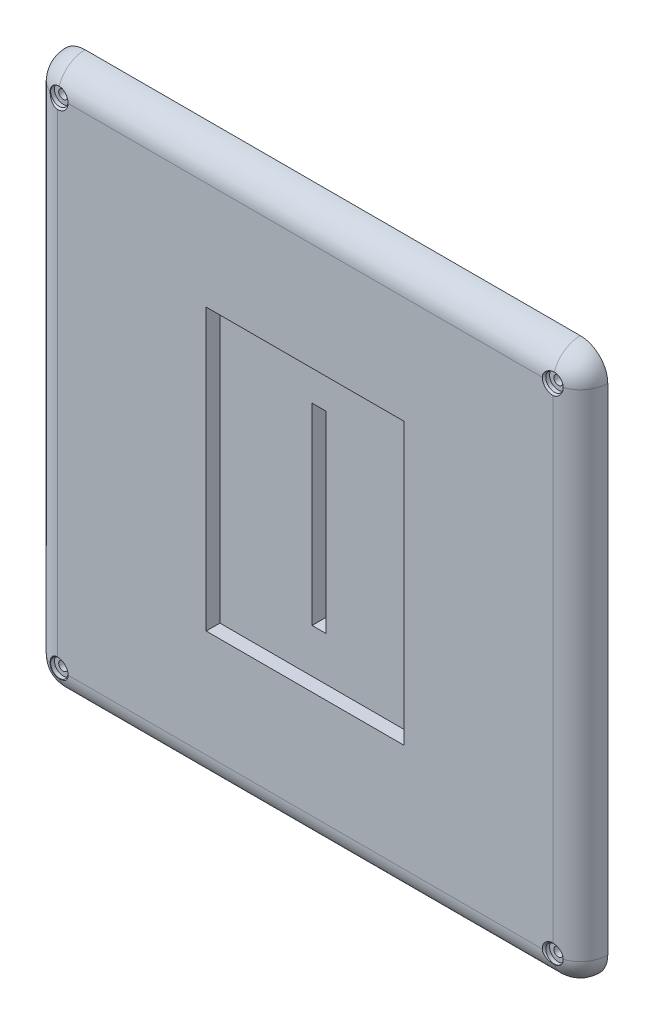
SolidWorks part; units mm, degrees
ref_plane "Alzado" through (0, 0, 0) normal (0, 0, 1) x (1, 0, 0)
ref_plane "Planta" through (0, 0, 0) normal (0, 1, 0) x (1, 0, 0)
ref_plane "Vista lateral" through (0, 0, 0) normal (1, 0, 0) x (0, 0, -1)
sketch "Croquis3" plane through (0, 0, 0) normal (0, 0, 1) x (1, 0, 0)
  line L1 (-100, -100) -> (100, -100)
  line L2 (-100, -100) -> (-100, 100)
  line L3 (-100, 100) -> (100, 100)
  line L4 (100, -100) -> (100, 100)
  line L5 (-100, -100) -> (100, 100) construction
  line L6 (-100, 100) -> (100, -100) construction
  point P0 (0, 0)
  dimension "D1" = 200
  dimension "D2" = 200
extrude "Saliente-Extruir1" add sketch "Croquis3" along normal blind 10
sketch "Croquis4" plane through (0, 0, 10) normal (0, 0, 1) x (1, 0, 0)
  line L0 (-100, -100) -> (100, -100) construction
  line L1 (0, -100) -> (0, 100) construction
  line L2 (100, 100) -> (-100, 100) construction
  line L4 (-36, 51) -> (36, 51)
  line L5 (-36, 51) -> (-36, -51)
  line L6 (-36, -51) -> (36, -51)
  line L7 (36, 51) -> (36, -51)
  line L8 (-36, 51) -> (36, -51) construction
  line L9 (-36, -51) -> (36, 51) construction
  point P8 (0, 0)
  dimension "D1" = 102
  dimension "D2" = 72
extrude "Cortar-Extruir2" cut sketch "Croquis4" against normal blind 5
sketch "Croquis5" plane through (0, 0, 10) normal (0, 0, 1) x (1, 0, 0)
  line L0 (-100, -100) -> (100, -100) construction
  line L1 (0, -100) -> (0, 100) construction
  line L2 (100, 100) -> (-100, 100) construction
  line L4 (-2.5, 35) -> (2.5, 35)
  line L5 (-2.5, 35) -> (-2.5, -35)
  line L6 (-2.5, -35) -> (2.5, -35)
  line L7 (2.5, 35) -> (2.5, -35)
  line L8 (-2.5, 35) -> (2.5, -35) construction
  line L9 (-2.5, -35) -> (2.5, 35) construction
  point P8 (0, 0)
  dimension "D1" = 70
  dimension "D2" = 5
extrude "Cortar-Extruir3" cut sketch "Croquis5" against normal through all
fillet "Redondeo1" radius 10 8 edges at (-100, 0, 10) (0, -100, 10) (100, 0, 10) (100, -100, 5) (-100, -100, 5) (-100, 100, 5) (100, 100, 5) (0, 100, 10)
fillet "Redondeo2" radius 10 1 edges at (97.0711, 97.0711, 7.0711)
fillet "Redondeo3" radius 10 1 edges at (-97.0711, -97.0711, 7.0711)
fillet "Redondeo4" radius 10 1 edges at (97.0711, -97.0711, 7.0711)
fillet "Redondeo5" radius 10 1 edges at (-97.0711, 97.0711, 7.0711)
hole_wizard "Refrentado para tornillo con cabeza troncocónica de #45" positions "Croquis15" profile "Croquis16" counterbore size "#4" standard "Ansi Inch" end condition through all
sketch "Croquis15" plane through (0, 0, 10) normal (0, 0, 1) x (1, 0, 0)
  line L0 (90, 90) -> (-90, 90) construction
  line L1 (90, -90) -> (90, 90) construction
  line L2 (-90, 90) -> (-90, -90) construction
  line L3 (-90, -90) -> (90, -90) construction
  point P0 (-90, 90)
  point P3 (90, 90)
  point P9 (90, -90)
  point P12 (-90, -90)
sketch "Croquis16" plane through (-90, 90, 10) normal (1, 0, 0) x (0, -1, 0)
  line L0 (0, 0) -> (0, 10)
  line L1 (0, 10) -> (1.6319, 10)
  line L3 (1.6319, 10) -> (1.632, 2.032)
  line L4 (3.175, 2.032) -> (1.632, 2.032)
  line L5 (3.175, 2.032) -> (3.175, 0.635)
  line L6 (3.175, 0.635) -> (3.81, 0)
  line L7 (3.81, 0) -> (0, 0)
  line L8 (-3.175, 0.635) -> (-3.81, 0) construction
  line L11 (0, -6.35) -> (0, 107.95) construction
  dimension "Diámetro de taladro hasta el siguiente" = 3.2639
  dimension "Profundidad de taladro hasta el siguiente" = 10
  dimension "Diámetro de refrentado" = 6.35
  dimension "Profundidad de refrentado" = 2.032
  dimension "Diámetro de avellanado cercano" = 7.62
  dimension "Ángulo de avellanado cercano" = 90
